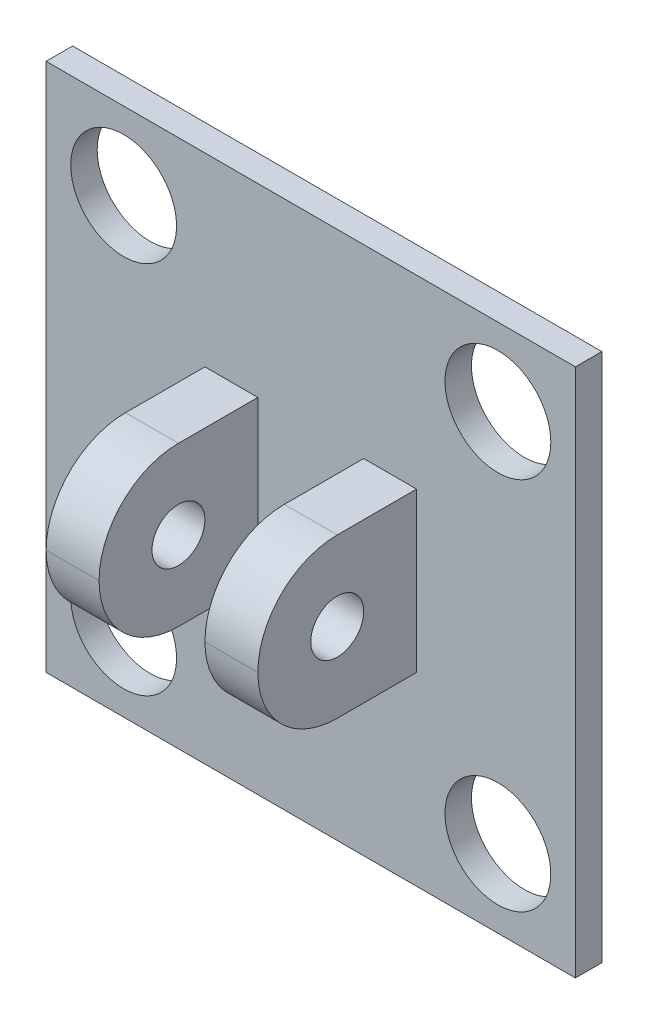
SolidWorks part; units mm, degrees
ref_plane "前视基准面" through (0, 0, 0) normal (0, 0, 1) x (1, 0, 0)
ref_plane "上视基准面" through (0, 0, 0) normal (0, 1, 0) x (1, 0, 0)
ref_plane "右视基准面" through (0, 0, 0) normal (1, 0, 0) x (0, 0, -1)
other "Configuration Table"
sketch "Sketch1" plane through (0, 0, 0) normal (0, 0, 1) x (1, 0, 0)
  line L0 (0, 25) -> (0, 0) construction
  line L1 (-25, -25) -> (25, -25)
  line L2 (-25, -25) -> (-25, 25)
  line L3 (-25, 25) -> (25, 25)
  line L4 (25, -25) -> (25, 25)
  line L5 (-25, -25) -> (25, 25) construction
  line L6 (-25, 25) -> (25, -25) construction
  line L7 (0, 0) -> (25, 0) construction
  line L8 (25, 0) -> (12.5, 0) construction
  line L9 (0, 0) -> (17.6777, 17.6777) construction
  circle A0 centre (17.6777, 17.6777) radius 5
  circle A4 centre (-17.6777, 17.6777) radius 5
  circle A5 centre (17.6777, -17.6777) radius 5
  circle A6 centre (-17.6777, -17.6777) radius 5
  point P10 (0, 0)
  point P11 (0, 0)
  point P16 (0, 0)
  point P18 (0, 0)
  dimension "D2" = 10
  dimension "D1" = 50
  dimension "D3" = 25
extrude "Boss-Extrude1" add sketch "Sketch1" along normal blind 2.5
sketch "Sketch2" plane through (0, 0, 2.5) normal (0, 0, 1) x (1, 0, 0)
  line L1 (-10, -7.5) -> (10, -7.5)
  line L2 (-10, -7.5) -> (-10, 7.5)
  line L3 (-10, 7.5) -> (10, 7.5)
  line L4 (10, -7.5) -> (10, 7.5)
  line L5 (-10, -7.5) -> (10, 7.5) construction
  line L6 (-10, 7.5) -> (10, -7.5) construction
  line L7 (-5, -7.5) -> (5, -7.5)
  line L8 (-5, -7.5) -> (-5, 7.5)
  line L9 (-5, 7.5) -> (5, 7.5)
  line L10 (5, -7.5) -> (5, 7.5)
  line L11 (-5, -7.5) -> (5, 7.5) construction
  line L12 (-5, 7.5) -> (5, -7.5) construction
  point P0 (0, 0)
  point P6 (0, 0)
  dimension "D1" = 10
  dimension "D2" = 20
  dimension "D3" = 15
extrude "Boss-Extrude2" add sketch "Sketch2" along normal blind 15 contours L1 L8 L3 L2 | L10 L1 L4 L3 region at (-7.5, 0, 2.5) region at (7.5, 0, 2.5)
sketch "Sketch3" plane through (10, 0, 0) normal (1, 0, 0) x (0, 0, -1)
  line L0 (-17.5, 0) -> (-2.5, 0) construction
  line L1 (-17.5, -7.5) -> (-17.5, 7.5) construction
  line L2 (-2.5, -7.5) -> (-2.5, 7.5) construction
  line L3 (-2.5, 0) -> (-10, 0) construction
  circle A0 centre (-10, 0) radius 2.5
  dimension "D1" = 5
extrude "Cut-Extrude1" cut sketch "Sketch3" against normal through all
fillet "Fillet1" radius 7.5 4 edges at (-7.5, 7.5, 17.5) (-7.5, -7.5, 17.5) (7.5, -7.5, 17.5) (7.5, 7.5, 17.5)
